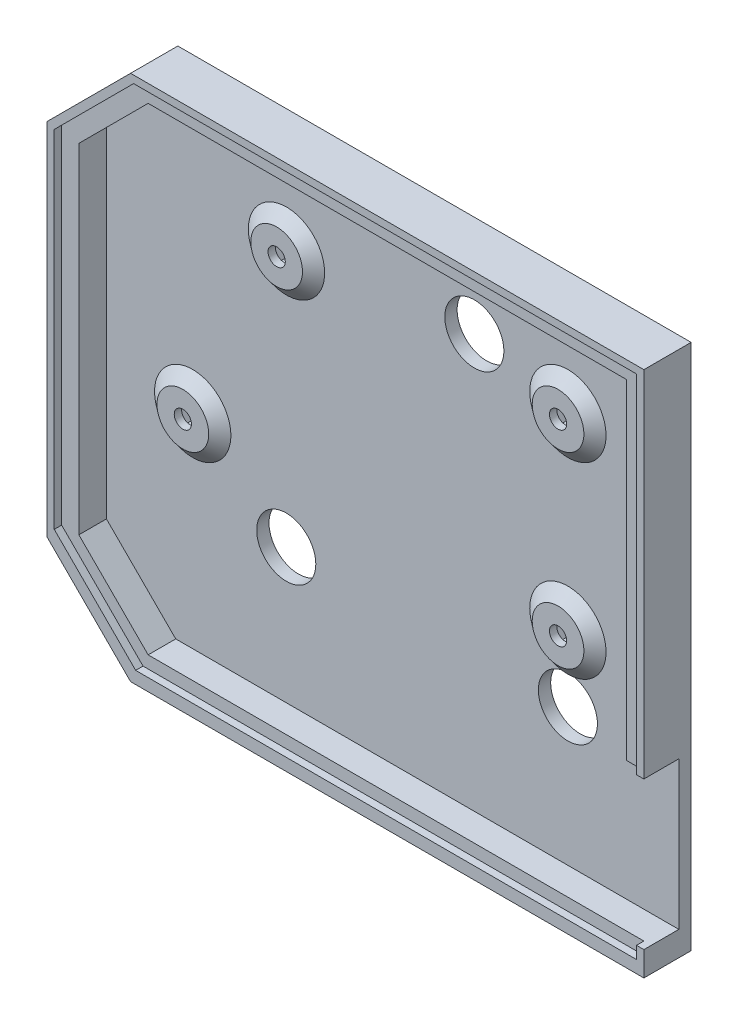
SolidWorks part; units mm, degrees
ref_plane "Plan de face" through (0, 0, 0) normal (0, 0, 1) x (1, 0, 0)
ref_plane "Plan de dessus" through (0, 0, 0) normal (0, 1, 0) x (1, 0, 0)
ref_plane "Plan de droite" through (0, 0, 0) normal (1, 0, 0) x (0, 0, -1)
sketch "Esquisse1" plane through (0, 0, 0) normal (0, 0, 1) x (1, 0, 0)
  line L0 (0, -85) -> (17, -102)
  line L4 (121.25, 5) -> (121.25, -102)
  line L5 (17, 5) -> (0, -12)
  line L7 (121.25, 5) -> (17, 5)
  line L8 (0, -12) -> (0, -85)
  line L9 (17, -102) -> (121.25, -102)
  dimension "D1" = 107
  dimension "D2" = 121.25
  dimension "D3" = 17
  dimension "D4" = 17
  dimension "D5" = 17
  dimension "D6" = 17
extrude "Boss.-Extru.1" add sketch "Esquisse1" along normal blind 2.5
sketch "Esquisse2" plane through (0, 0, 2.5) normal (0, 0, 1) x (1, 0, 0)
  line L0 (0, -12) -> (0, -85) construction
  line L1 (5, 0) -> (116.25, 0) construction
  line L2 (5, 0) -> (5, -97) construction
  line L3 (5, -97) -> (116.25, -97) construction
  line L4 (116.25, 0) -> (116.25, -97) construction
  line L5 (17, -102) -> (121.25, -102) construction
  line L6 (121.25, -102) -> (121.25, 5) construction
  line L7 (121.25, 5) -> (17, 5) construction
  line L9 (5, -82.9289) -> (19.0711, -97)
  line L10 (0, -85) -> (17, -102) construction
  line L11 (5, -14.0711) -> (19.0711, 0)
  line L12 (17, 5) -> (0, -12) construction
  line L13 (116.25, 0) -> (19.0711, 0)
  line L14 (5, -14.0711) -> (5, -82.9289)
  line L15 (19.0711, -97) -> (116.25, -97)
  line L16 (121.25, 5) -> (121.25, -102) construction
  line L17 (121.25, -102) -> (17, -102)
  line L18 (17, -102) -> (0, -85)
  line L19 (0, -85) -> (0, -12)
  line L20 (0, -12) -> (17, 5)
  line L21 (17, 5) -> (121.25, 5)
  line L30 (121.25, -2.5) -> (121.25, 5)
  line L31 (116.25, -97) -> (121.25, -97)
  line L32 (121.25, -97) -> (121.25, -102)
  line L33 (116.25, 0) -> (116.25, -67)
  line L34 (116.25, -67) -> (121.25, -67)
  line L35 (121.25, -67) -> (121.25, -2.5)
  point P24 (118.75, -97)
  dimension "D1" = 5
  dimension "D2" = 5
  dimension "D3" = 5
  dimension "D4" = 5
  dimension "D5" = 5
  dimension "D6" = 5
  dimension "D7" = 30
extrude "Boss.-Extru.2" add sketch "Esquisse2" along normal blind 7.1
sketch "Esquisse4" plane through (0, 0, 2.5) normal (0, 0, 1) x (1, 0, 0)
  line L0 (116.25, 0) -> (116.25, -67) construction
  line L1 (19.0711, 0) -> (116.25, 0) construction
  point P0 (41.57, -17.53)
  point P1 (22.52, -55.63)
  point P2 (98.72, -55.63)
  point P3 (98.72, -17.53)
  dimension "D1" = 17.53
  dimension "D2" = 17.53
  dimension "D3" = 38.1
  dimension "D4" = 57.15
  dimension "D5" = 76.2
ref_axis "Axe1" through (98.72, -55.63, 2.5) along (0, 0, 1)
ref_axis "Axe2" through (22.52, -55.63, 2.5) along (0, 0, 1)
ref_axis "Axe3" through (41.57, -17.53, 2.5) along (0, 0, 1)
ref_axis "Axe4" through (98.72, -17.53, 2.5) along (0, 0, 1)
ref_plane "Plan1" through (0, -55.63, 0) normal (0, -1, 0) x (-1, 0, 0)
ref_plane "Plan2" through (0, -17.53, 0) normal (0, 1, 0) x (1, 0, 0)
sketch "Esquisse9" plane through (0, -55.63, 0) normal (0, -1, 0) x (-1, 0, 0)
  line L0 (-96.97, -2.5) -> (-90.97, -2.5)
  line L1 (-90.97, -2.5) -> (-93.47, -4.5)
  line L2 (-93.47, -4.5) -> (-96.97, -4.5)
  line L3 (-96.97, -4.5) -> (-96.97, -2.5)
  line L4 (-98.72, -2.5) -> (-98.72, -52.4632) construction
  point P0 (-98.5795, 0)
  dimension "D1" = 2
  dimension "D2" = 1.75
  dimension "D3" = 3.5
  dimension "D4" = 6
ref_point "Point1"
ref_point "Point2"
ref_point "Point3"
ref_point "Point4"
revolve "Révolution1" add sketch "Esquisse9" angle 360 about axis through (98.72, -55.63, 2.5) along (0, 0, 1)
sketch "Esquisse11" plane through (0, -55.63, 0) normal (0, -1, 0) x (-1, 0, 0)
  line L0 (-24.27, -2.5) -> (-30.27, -2.5)
  line L1 (-30.27, -2.5) -> (-27.77, -4.5)
  line L2 (-27.77, -4.5) -> (-24.27, -4.5)
  line L3 (-24.27, -4.5) -> (-24.27, -2.5)
  line L4 (-22.52, -2.5) -> (-22.52, -52.4632) construction
  dimension "D1" = 1.75
  dimension "D2" = 3.5
  dimension "D3" = 6
  dimension "D4" = 2
revolve "Révolution2" add sketch "Esquisse11" angle 360 about axis through (22.52, -55.63, 2.5) along (0, 0, 1)
sketch "Esquisse12" plane through (0, -17.53, 0) normal (0, 1, 0) x (1, 0, 0)
  line L0 (96.97, -2.5) -> (90.97, -2.5)
  line L1 (90.97, -2.5) -> (93.47, -4.5)
  line L2 (93.47, -4.5) -> (96.97, -4.5)
  line L3 (96.97, -4.5) -> (96.97, -2.5)
  line L4 (98.72, -2.5) -> (98.72, -52.4632) construction
  dimension "D1" = 1.75
  dimension "D2" = 2
  dimension "D3" = 3.5
  dimension "D4" = 6
revolve "Révolution3" add sketch "Esquisse12" angle 360 about axis through (98.72, -17.53, 2.5) along (0, 0, 1)
sketch "Esquisse13" plane through (0, -17.53, 0) normal (0, 1, 0) x (1, 0, 0)
  line L0 (43.32, -2.5) -> (49.32, -2.5)
  line L1 (49.32, -2.5) -> (46.82, -4.5)
  line L2 (46.82, -4.5) -> (43.32, -4.5)
  line L3 (43.32, -4.5) -> (43.32, -2.5)
  line L4 (41.57, -2.5) -> (41.57, -52.4632) construction
  dimension "D1" = 1.75
  dimension "D2" = 3.5
  dimension "D3" = 6
  dimension "D4" = 2
revolve "Révolution4" add sketch "Esquisse13" angle 360 about axis through (41.57, -17.53, 2.5) along (0, 0, 1)
hole_wizard "Dégagement M31" positions "Esquisse14" profile "Esquisse15" hole size "M3" standard "Ansi Metric" end condition up to next
sketch "Esquisse14" plane through (0, 0, 2.5) normal (0, 0, 1) x (1, 0, 0)
  point P0 (98.72, -55.63)
  point P3 (22.52, -55.63)
  point P6 (98.72, -17.53)
  point P9 (41.57, -17.53)
sketch "Esquisse15" plane through (98.72, -55.63, 2.5) normal (1, 0, 0) x (0, -1, 0)
  line L0 (0, 0) -> (0, 2.5)
  line L1 (0, 2.5) -> (1.8, 2.5)
  line L2 (1.8, 2.5) -> (1.8, 0)
  line L5 (1.8, 0) -> (0, 0)
  line L11 (0, -6.35) -> (0, 107.95) construction
  dimension "Diamètre du perçage jusqu'au prochain" = 3.6
  dimension "Profondeur du perçage jusqu'au prochain" = 2.5
ref_point "Point5"
ref_point "Point6"
ref_point "Point7"
ref_point "Point8"
sketch "Esquisse16" plane through (0, 0, 0) normal (0, 0, -1) x (-1, 0, 0)
  line L0 (-121.25, 5) -> (-17, 5) construction
  line L1 (-24.0788, -52.93) -> (-25.6377, -55.63)
  line L2 (-25.6377, -55.63) -> (-24.0788, -58.33)
  line L3 (-24.0788, -58.33) -> (-20.9612, -58.33)
  line L4 (-20.9612, -58.33) -> (-19.4023, -55.63)
  line L5 (-19.4023, -55.63) -> (-20.9612, -52.93)
  line L6 (-20.9612, -52.93) -> (-24.0788, -52.93)
  line L7 (-100.2788, -52.93) -> (-101.8377, -55.63)
  line L8 (-101.8377, -55.63) -> (-100.2788, -58.33)
  line L9 (-100.2788, -58.33) -> (-97.1612, -58.33)
  line L10 (-97.1612, -58.33) -> (-95.6023, -55.63)
  line L11 (-95.6023, -55.63) -> (-97.1612, -52.93)
  line L12 (-97.1612, -52.93) -> (-100.2788, -52.93)
  line L13 (-100.2788, -14.83) -> (-101.8377, -17.53)
  line L14 (-101.8377, -17.53) -> (-100.2788, -20.23)
  line L15 (-100.2788, -20.23) -> (-97.1612, -20.23)
  line L16 (-97.1612, -20.23) -> (-95.6023, -17.53)
  line L17 (-95.6023, -17.53) -> (-97.1612, -14.83)
  line L18 (-97.1612, -14.83) -> (-100.2788, -14.83)
  line L19 (-43.1288, -14.83) -> (-44.6877, -17.53)
  line L20 (-44.6877, -17.53) -> (-43.1288, -20.23)
  line L21 (-43.1288, -20.23) -> (-40.0112, -20.23)
  line L22 (-40.0112, -20.23) -> (-38.4523, -17.53)
  line L23 (-38.4523, -17.53) -> (-40.0112, -14.83)
  line L24 (-40.0112, -14.83) -> (-43.1288, -14.83)
  circle A0 centre (-22.52, -55.63) radius 2.7 construction
  circle A1 centre (-98.72, -55.63) radius 2.7 construction
  circle A2 centre (-98.72, -17.53) radius 2.7 construction
  circle A3 centre (-41.57, -17.53) radius 2.7 construction
  dimension "D1" = 5.4
  dimension "D2" = 5.4
  dimension "D3" = 5.4
  dimension "D4" = 5.4
extrude "Enlèv. mat.-Extru.2" cut sketch "Esquisse16" against normal blind 3
sketch "Esquisse17" plane through (0, 0, 9.6) normal (0, 0, 1) x (1, 0, 0)
  line L0 (17, -102) -> (121.25, -102) construction
  line L1 (119.75, -99.5) -> (1.5, -99.5) construction
  line L2 (119.75, -99.5) -> (119.75, 3.5)
  line L3 (119.75, 3.5) -> (1.5, 3.5) construction
  line L4 (1.5, -99.5) -> (1.5, 3.5) construction
  line L5 (121.25, -102) -> (121.25, -97) construction
  line L6 (0, -12) -> (0, -85) construction
  line L7 (121.25, 5) -> (17, 5) construction
  line L10 (5, -14.0711) -> (0, -12) construction
  line L11 (19.0711, 0) -> (17, 5) construction
  line L12 (119.75, 3.5) -> (116.25, 0) construction
  line L17 (17.6213, 3.5) -> (119.75, 3.5)
  line L18 (15.5687, -97.0332) -> (-9.8376, -71.6268) construction
  line L19 (0, -85) -> (17, -102) construction
  line L20 (119.75, -99.5) -> (18.0355, -99.5)
  line L21 (18.0355, -99.5) -> (1.5, -82.9645)
  line L22 (1.5, -82.9645) -> (1.5, -12.6213)
  line L23 (1.5, -12.6213) -> (17.6213, 3.5)
  dimension "D1" = 2.5
  dimension "D2" = 1.5
  dimension "D3" = 1.5
  dimension "D4" = 1.5
  dimension "D5" = 2.5
extrude "Enlèv. mat.-Extru.3" cut sketch "Esquisse17" against normal blind 1.5
sketch "Esquisse20" plane through (0, 0, 2.5) normal (0, 0, 1) x (1, 0, 0)
  circle A0 centre (98.72, -69.13) radius 6
  circle A1 centre (41.52, -69.63) radius 6
  circle A2 centre (79.72, -13.03) radius 6
  dimension "D1" = 13.5
  dimension "D3" = 19
  dimension "D5" = 19
  dimension "D2" = 0
  dimension "D4" = 14
  dimension "D6" = 4.5
extrude "Enlèv. mat.-Extru.4" cut sketch "Esquisse20" against normal blind 10
